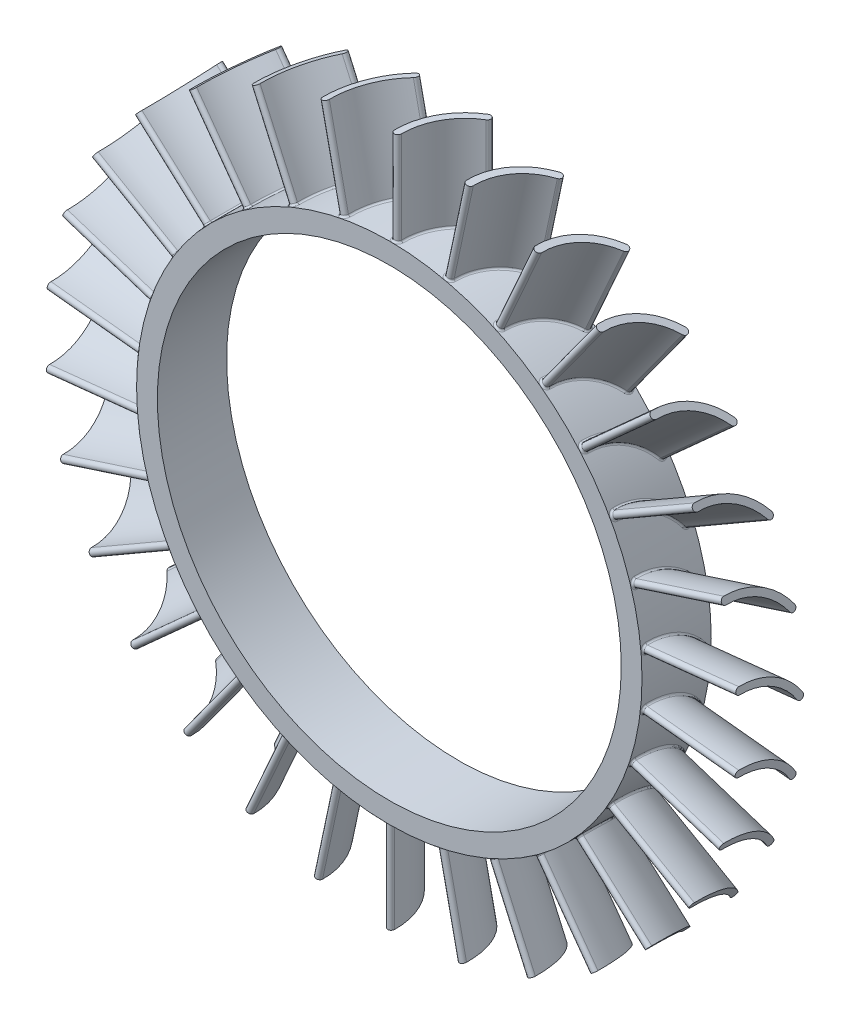
SolidWorks part; units mm, degrees
ref_plane "Front Plane" through (0, 0, 0) normal (0, 0, 1) x (1, 0, 0)
ref_plane "Top Plane" through (0, 0, 0) normal (0, 1, 0) x (1, 0, 0)
ref_plane "Right Plane" through (0, 0, 0) normal (1, 0, 0) x (0, 0, -1)
sketch "Sketch1" plane through (0, 0, 0) normal (0, 0, 1) x (1, 0, 0)
  circle A0 centre (0, 0) radius 73
  circle A1 centre (0, 0) radius 67
  dimension "D1" = 134
  dimension "D2" = 146
extrude "Boss-Extrude1" add sketch "Sketch1" along normal mid plane 20
sketch "Sketch2" plane through (0, 0, 0) normal (0, 1, 0) x (1, 0, 0)
  line L0 (-73, -10) -> (73, -10) construction
  line L1 (67, 10) -> (-67, 10) construction
  arc A0 (-0.0154, -8.5) -> (9.6648, 9) centre (19.9812, -8.1339) cw
  arc A1 (1.9843, -8.4634) -> (10.6964, 7.2866) centre (19.9812, -8.1339) cw
  arc A3 (-0.0154, -8.5) -> (1.9843, -8.4634) centre (0.9844, -8.4817) ccw
  arc A4 (9.6648, 9) -> (10.6964, 7.2866) centre (10.1806, 8.1433) cw
  dimension "D3" = 20
  dimension "D1" = 1.5
  dimension "D2" = 1
  dimension "D4" = 2
extrude "Boss-Extrude2" add sketch "Sketch2" along normal blind 32 from offset 68
fillet "Fillet1" radius 0.5 4 edges at (0.8792, 72.9947, 9.4761) (1.2928, 72.9886, 1.0105) (9.2833, 72.4073, -7.7018) (2.4685, 72.9583, 3.9741)
pattern_circular "CirPattern1" count 30 over 360 about axis through (0, 0, 10) along (0, 0, -1) of "Boss-Extrude2", "Fillet1"
